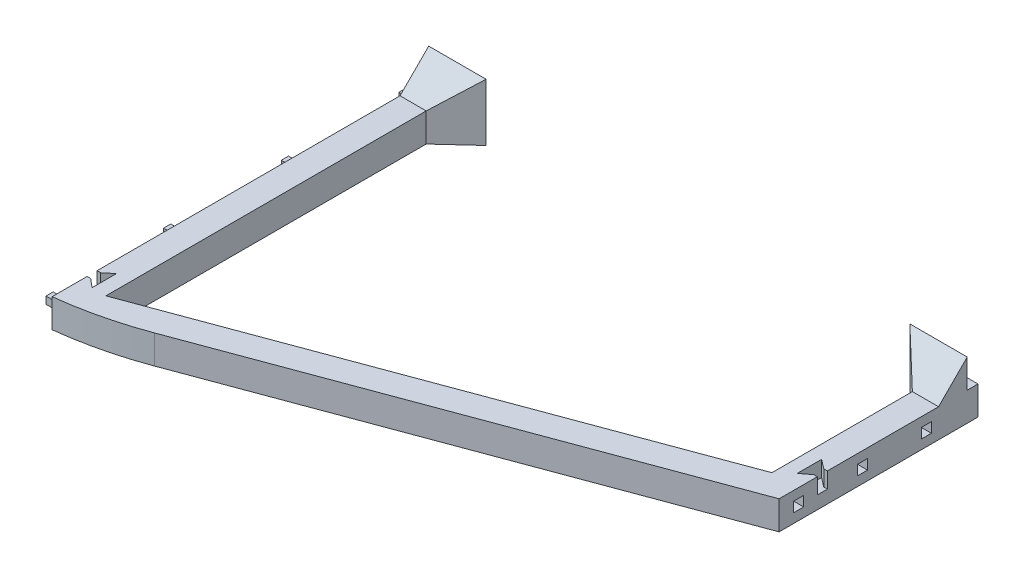
SolidWorks part; units mm, degrees
ref_plane "Přední rovina" through (0, 0, 0) normal (0, 0, 1) x (1, 0, 0)
ref_plane "Horní rovina" through (0, 0, 0) normal (0, 1, 0) x (1, 0, 0)
ref_plane "Pravá rovina" through (0, 0, 0) normal (1, 0, 0) x (0, 0, -1)
sketch "Skica1" plane through (0, 0, 0) normal (0, 1, 0) x (1, 0, 0)
  line L0 (0, 0) -> (0, -111)
  line L1 (0, -111) -> (150.15, -55.45)
  line L2 (150.15, -55.45) -> (150.15, 0)
  line L3 (150.15, 0) -> (142.85, 0)
  line L4 (142.85, 0) -> (142.85, -50.1539)
  line L5 (142.85, -50.1539) -> (7.3, -100.3024)
  line L6 (7.3, -100.3024) -> (7.3, 0)
  line L7 (7.3, 0) -> (0, 0)
  dimension "D1" = 7.3
  dimension "D2" = 7.3
  dimension "D3" = 111
  dimension "D4" = 7.5
  dimension "D5" = 150.15
  dimension "D6" = 55.45
extrude "Přidat vysunutím1" add sketch "Skica1" along normal blind 8
sketch "Skica2" plane through (0, 8, 0) normal (0, 1, 0) x (1, 0, 0)
  line L5 (0, -95.45) -> (1, -95.45)
  line L6 (0, 0) -> (0, -111) construction
  line L7 (1, -95.45) -> (3.4, -93.45)
  line L8 (3.4, -93.45) -> (3.4, -100.25)
  line L9 (3.4, -100.25) -> (1, -98.25)
  line L10 (1, -98.25) -> (0, -98.25)
  line L11 (0, -98.25) -> (0, -95.45)
  dimension "D1" = 6.8
  dimension "D2" = 2.8
  dimension "D3" = 1
  dimension "D4" = 1
  dimension "D5" = 2
  dimension "D6" = 3.4
  dimension "D7" = 10.75
extrude "Odebrat vysunutím1" cut sketch "Skica2" against normal blind 4.4
sketch "Skica3" plane through (0, 0, 0) normal (-1, 0, 0) x (0, 0, 1)
  line L0 (0, 8) -> (0, 0) construction
  line L1 (5.3, 5) -> (7.3, 5)
  line L2 (5.3, 5) -> (5.3, 3)
  line L3 (5.3, 3) -> (7.3, 3)
  line L4 (7.3, 5) -> (7.3, 3)
  line L5 (38.1, 5) -> (40.1, 5)
  line L6 (38.1, 5) -> (38.1, 3)
  line L7 (38.1, 3) -> (40.1, 3)
  line L8 (40.1, 5) -> (40.1, 3)
  line L9 (70.9, 5) -> (72.9, 5)
  line L10 (70.9, 5) -> (70.9, 3)
  line L11 (70.9, 3) -> (72.9, 3)
  line L12 (72.9, 5) -> (72.9, 3)
  line L17 (0, 8) -> (95.45, 8) construction
  line L18 (98.25, 8) -> (111, 8) construction
  line L19 (103.7, 5) -> (105.7, 5)
  line L20 (103.7, 5) -> (103.7, 3)
  line L21 (103.7, 3) -> (105.7, 3)
  line L22 (105.7, 5) -> (105.7, 3)
  point P16 (5.3, 4)
  dimension "D1" = 5.3
  dimension "D2" = 2
  dimension "D3" = 2
  dimension "D4" = 3
  dimension "D5" = 2
  dimension "D6" = 2
  dimension "D7" = 3
  dimension "D8" = 30.8
  dimension "D9" = 2
  dimension "D10" = 2
  dimension "D11" = 3
  dimension "D12" = 30.8
  dimension "D13" = 2
  dimension "D14" = 2
  dimension "D15" = 3
  dimension "D16" = 30.8
extrude "Přidat vysunutím2" add sketch "Skica3" along normal blind 4
sketch "Skica5" plane through (0, 8, 0) normal (0, 1, 0) x (1, 0, 0)
  line L0 (0, 0) -> (0, -95.45) construction
  line L1 (0, -3) -> (16, -3)
  line L2 (0, -3) -> (0, -11)
  line L3 (0, -11) -> (16, -11)
  line L4 (16, -3) -> (16, -11)
  line L5 (150.15, -55.45) -> (150.15, 0) construction
  line L6 (150.15, -3) -> (134.15, -3)
  line L7 (150.15, -3) -> (150.15, -11)
  line L8 (150.15, -11) -> (134.15, -11)
  line L9 (134.15, -3) -> (134.15, -11)
  line L10 (150.15, 0) -> (142.85, 0) construction
  line L11 (7.3, 0) -> (0, 0) construction
  dimension "D1" = 8
  dimension "D2" = 8
  dimension "D3" = 16
  dimension "D4" = 16
  dimension "D5" = 3
  dimension "D6" = 3
extrude "Přidat vysunutím3" add sketch "Skica5" against normal blind 16 from offset 8
sketch "Skica6" plane through (150.15, 0, 0) normal (1, 0, 0) x (0, 0, -1)
  line L0 (-11, 8) -> (-11, 16)
  line L1 (-11, 16) -> (-3, 16)
  line L2 (-3, 16) -> (-11, 8)
extrude "Odebrat vysunutím3" cut sketch "Skica6" against normal through all
sketch "Skica7" plane through (0, 0, 0) normal (0, -1, 0) x (1, 0, 0)
  line L0 (7.3, 11) -> (16, 3)
  line L1 (16, 3) -> (16, 11)
  line L2 (16, 11) -> (7.3, 11)
  line L3 (134.15, 3) -> (134.15, 11)
  line L4 (134.15, 11) -> (142.85, 11)
  line L5 (142.85, 11) -> (134.15, 3)
extrude "Odebrat vysunutím4" cut sketch "Skica7" against normal through all
sketch "Skica4" plane through (150.15, 0, 0) normal (1, 0, 0) x (0, 0, -1)
  line L0 (-55.45, 8) -> (-11, 8) construction
  line L1 (-51.4, 5.4) -> (-48.6, 5.4)
  line L2 (-51.4, 5.4) -> (-51.4, 2.6)
  line L3 (-51.4, 2.6) -> (-48.6, 2.6)
  line L4 (-48.6, 5.4) -> (-48.6, 2.6)
  line L5 (-33.6, 5.4) -> (-30.8, 5.4)
  line L6 (-33.6, 5.4) -> (-33.6, 2.6)
  line L7 (-33.6, 2.6) -> (-30.8, 2.6)
  line L8 (-30.8, 5.4) -> (-30.8, 2.6)
  line L9 (-15.8, 5.4) -> (-13, 5.4)
  line L10 (-15.8, 5.4) -> (-15.8, 2.6)
  line L11 (-15.8, 2.6) -> (-13, 2.6)
  line L12 (-13, 5.4) -> (-13, 2.6)
  line L14 (0, 8) -> (0, 0) construction
  point P16 (-30.8, 4)
  dimension "D1" = 2.8
  dimension "D2" = 2.8
  dimension "D3" = 2.6
  dimension "D4" = 2.8
  dimension "D5" = 2.8
  dimension "D6" = 2.6
  dimension "D7" = 2.8
  dimension "D8" = 2.8
  dimension "D9" = 2.6
  dimension "D10" = 13
  dimension "D11" = 15
  dimension "D12" = 15
extrude "Odebrat vysunutím2" cut sketch "Skica4" against normal blind 4.4
sketch "Skica8" plane through (0, 8, 0) normal (0, 1, 0) x (1, 0, 0)
  line L6 (150.15, -42) -> (149.15, -42)
  line L7 (150.15, -55.45) -> (150.15, -11) construction
  line L8 (149.15, -42) -> (146.55, -40)
  line L9 (146.55, -40) -> (146.55, -46.8)
  line L10 (146.55, -46.8) -> (149.15, -44.8)
  line L11 (150.15, -44.8) -> (150.15, -42)
  line L12 (149.15, -44.8) -> (150.15, -44.8)
  line L13 (150.15, 0) -> (142.85, 0) construction
  point P10 (146.5, 0)
  dimension "D1" = 6.8
  dimension "D2" = 1
  dimension "D3" = 2.8
  dimension "D4" = 2
  dimension "D5" = 3.6
  dimension "D6" = 40
  dimension "D7" = 1
extrude "Odebrat vysunutím5" cut sketch "Skica8" against normal blind 4.4
sketch "Skica9" plane through (0, 8, 0) normal (0, 1, 0) x (1, 0, 0)
  line L0 (0, -108) -> (8.1089, -108)
  line L1 (0, -98.25) -> (0, -111) construction
  line L2 (0, -111) -> (150.15, -55.45) construction
  line L3 (8.1089, -108) -> (0, -111)
  line L4 (0, -111) -> (0, -108)
  dimension "D1" = 3
extrude "Odebrat vysunutím6" cut sketch "Skica9" against normal through all
fillet "Zaoblit1" radius 100 1 edges at (8.1089, 4, 108)
